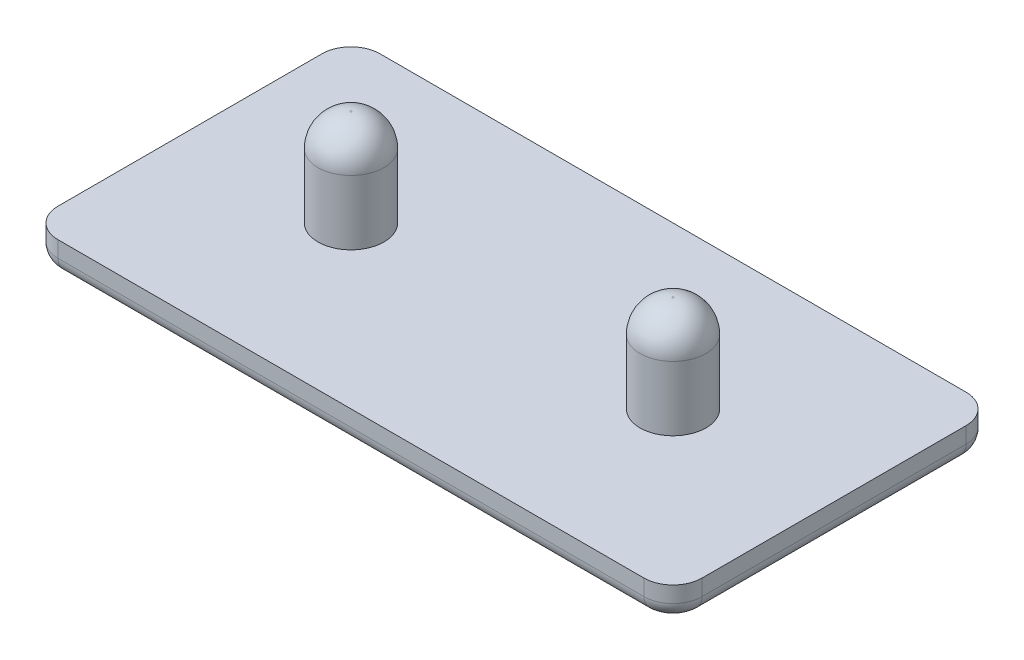
SolidWorks part; units mm, degrees
ref_plane "Front Plane" through (0, 0, 0) normal (0, 0, 1) x (1, 0, 0)
ref_plane "Top Plane" through (0, 0, 0) normal (0, 1, 0) x (1, 0, 0)
ref_plane "Right Plane" through (0, 0, 0) normal (1, 0, 0) x (0, 0, -1)
sketch "Sketch1" plane through (0, 0, 0) normal (0, 1, 0) x (1, 0, 0)
  line L0 (0, 10) -> (40, 10) construction
  line L1 (1.8, 0) -> (38.2, 0)
  line L2 (0, 1.8) -> (0, 18.2)
  line L3 (1.8, 20) -> (38.2, 20)
  line L4 (40, 1.8) -> (40, 18.2)
  arc A0 (0, 1.8) -> (1.8, 0) centre (1.8, 1.8) ccw
  arc A1 (38.2, 0) -> (40, 1.8) centre (38.2, 1.8) ccw
  arc A2 (40, 18.2) -> (38.2, 20) centre (38.2, 18.2) ccw
  arc A3 (1.8, 20) -> (0, 18.2) centre (1.8, 18.2) ccw
  circle A4 centre (10, 10) radius 2.05
  circle A5 centre (30, 10) radius 2.05
  point P7 (0, 0)
  point P10 (40, 0)
  point P15 (0, 20)
  dimension "D3" = 1.8
  dimension "D6" = 4.1
  dimension "D1" = 20
  dimension "D2" = 40
  dimension "D4" = 10
  dimension "D5" = 10
extrude "Boss-Extrude1" add sketch "Sketch1" along normal blind 2
extrude "Boss-Extrude2" add sketch "Sketch1<2>" along normal blind 8 contours A4 L0 | A5 L0 | L0 A5 | L0 A4 region at (30, 0, -9.13) region at (30, 0, -10.87) region at (10, 0, -9.13) region at (10, 0, -10.87)
sketch "Sketch1<2>" plane through (0, 0, 0) normal (0, 1, 0) x (1, 0, 0) same geometry as "Sketch1"
fillet "Fillet1" radius 2 2 edges at (10, 8, -7.95) (30, 8, -7.95)
fillet "Fillet2" radius 1 8 edges at (20, 0, 0) (39.4728, 0, -0.5272) (40, 0, -10) (39.4728, 0, -19.4728) (20, 0, -20) (0.5272, 0, -19.4728) (0, 0, -10) (0.5272, 0, -0.5272)
